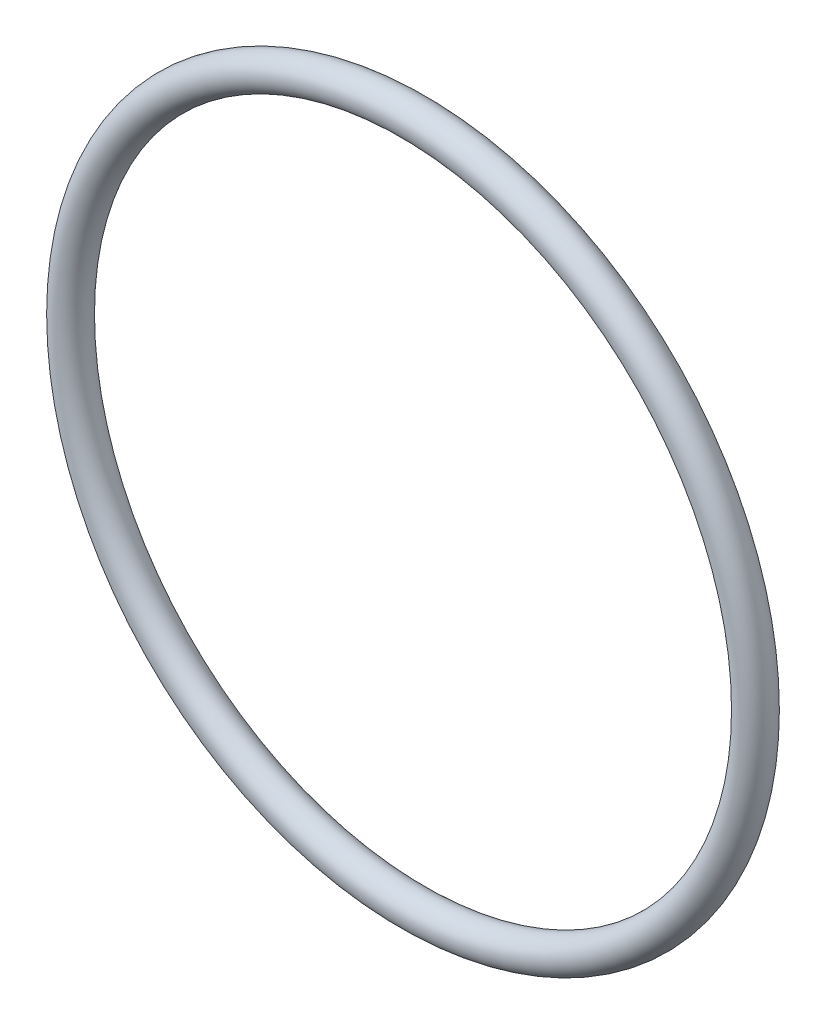
SolidWorks part; units mm, degrees
ref_plane "Front" through (0, 0, 0) normal (0, 0, 1) x (1, 0, 0)
ref_plane "Top" through (0, 0, 0) normal (0, 1, 0) x (1, 0, 0)
ref_plane "Right" through (0, 0, 0) normal (1, 0, 0) x (0, 0, -1)
sketch "Sketch1" plane through (0, 0, 0) normal (0, 0, 1) x (1, 0, 0)
  circle A0 centre (0, 0) radius 54.8
  dimension "d1" = 109.6
sketch "Sketch2" plane through (0, 0, 0) normal (0, 1, 0) x (1, 0, 0)
  circle A0 centre (-57.65, 0) radius 2.85
  point P2 (-54.8, 0)
  dimension "d2" = 5.7
sweep "Sweep1" add profiles "Sketch2" path "Sketch1"
ref_axis "Axis1" through (0, 0, -5.0798) along (0, 0, 1)
